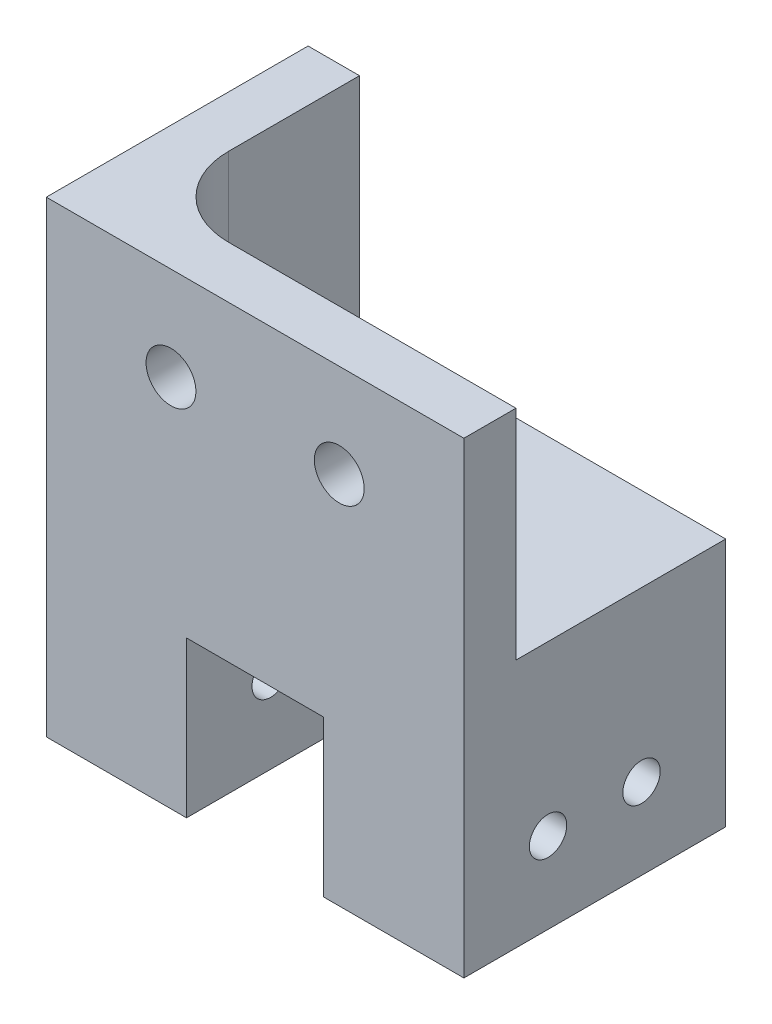
SolidWorks part; units mm, degrees
material "6061 Legierung"
ref_plane "Ebene vorne" through (0, 0, 0) normal (0, 0, 1) x (1, 0, 0)
ref_plane "Ebene oben" through (0, 0, 0) normal (0, 1, 0) x (1, 0, 0)
ref_plane "Ebene rechts" through (0, 0, 0) normal (1, 0, 0) x (0, 0, -1)
sketch "Skizze1" plane through (0, 0, 0) normal (0, 0, 1) x (1, 0, 0)
  line L13 (-11, 155) -> (11, 155)
  line L15 (11, 155) -> (11, 130)
  line L17 (11, 130) -> (33.5, 130)
  line L18 (33.5, 130) -> (33.5, 205)
  line L19 (33.5, 205) -> (-33.5, 205)
  line L23 (-33.5, 130) -> (-33.5, 205)
  line L24 (-11, 130) -> (-33.5, 130)
  line L25 (-11, 155) -> (-11, 130)
  point P16 (0, 205)
  point P19 (0, 155)
sketch "Skizze3" plane through (0, 0, 0) normal (0, 0, 1) x (1, 0, 0)
  line L9 (0, 205) -> (33.5, 205)
  line L10 (33.5, 205) -> (33.5, 130)
  line L11 (33.5, 130) -> (11, 130)
  line L12 (11, 130) -> (11, 155)
  line L13 (11, 155) -> (0, 155)
  line L14 (0, 205) -> (-33.5, 205)
  line L15 (-33.5, 205) -> (-33.5, 130)
  line L16 (-33.5, 130) -> (-11, 130)
  line L17 (-11, 130) -> (-11, 155)
  line L18 (-11, 155) -> (0, 155)
sketch "Skizze4" plane through (0, 0, 0) normal (1, 0, 0) x (0, 0, -1)
  line L0 (15, 0) -> (-15, 0)
  point P8 (0, 0)
extrude "Aufsatz-Linear austragen1" add sketch "Skizze3" along normal blind 21 and the other way blind 21
sketch "Skizze5" plane through (0, 0, 0) normal (0, 1, 0) x (1, 0, 0)
  line L1 (-12.6, 12.65) -> (25.15, 12.65)
  line L2 (25.15, 12.65) -> (25.15, -12.65)
  line L3 (25.15, -12.65) -> (-12.6, -12.65)
  line L5 (-12.6, 10.85) -> (23.35, 10.85)
  line L6 (23.35, 10.85) -> (23.35, -10.85)
  line L7 (23.35, -10.85) -> (-12.6, -10.85)
  arc A0 (-12.6, 12.65) -> (-12.6, -12.65) centre (-12.6, 0) ccw
  arc A1 (-12.6, 10.85) -> (-12.6, -10.85) centre (-12.6, 0) ccw
sketch "Skizze6" plane through (0, 205, 0) normal (0, 1, 0) x (1, 0, 0)
  line L0 (-25.25, 0) -> (-25.25, 21)
  line L1 (33.5, 21) -> (-33.5, 21) construction
  line L2 (-25.25, 21) -> (33.5, 21)
  line L3 (33.5, 21) -> (33.5, -21) construction
  line L4 (33.5, 21) -> (33.5, -12.65)
  line L5 (33.5, -12.65) -> (-12.6, -12.65)
  arc A0 (-12.6, 12.65) -> (-12.6, -12.65) centre (-12.6, 0) ccw construction
  arc A1 (-25.25, 0) -> (-12.6, -12.65) centre (-12.6, 0) ccw
sketch "StingHeigtPos" plane through (0, 0, 0) normal (0, 0, 1) x (1, 0, 0)
  line L0 (0, 170) -> (0, 570)
extrude "Schnitt-Linear austragen1" cut sketch "Skizze6" against normal up to vertex (35 mm away) up to point (0, 170, 0)
sketch "Holes" plane through (0, 0, 0) normal (0, 0, 1) x (1, 0, 0)
  circle A0 centre (13.5, 190) radius 4
  circle A1 centre (-13.5, 190) radius 4
sketch "Skizze9" plane through (0, 0, 0) normal (0, 0, 1) x (1, 0, 0)
  circle A0 centre (-13.5, 190) radius 4
  circle A1 centre (13.5, 190) radius 4
extrude "Schnitt-Linear austragen2" cut sketch "Skizze9" along normal up to surface (21 mm away) up to face at (0, 155, 21)
sketch "Skizze10" plane through (0, 0, 0) normal (1, 0, 0) x (0, 0, -1)
  line L2 (0, 90) -> (21.451, 90) construction
  circle A0 centre (7.5, 37) radius 3
  circle A1 centre (-7.5, 37) radius 3
  circle A4 centre (-7.5, 143) radius 3
  circle A5 centre (7.5, 143) radius 3
sketch "Skizze11" plane through (0, 0, 0) normal (1, 0, 0) x (0, 0, -1)
  circle A0 centre (7.5, 143) radius 3
  circle A1 centre (-7.5, 143) radius 3
extrude "Schnitt-Linear austragen3" cut sketch "Skizze11" against normal up to surface and the other way up to surface up to face at (-33.5, 167.5, 0) other way up to face at (33.5, 168.3333, 4.2167)
